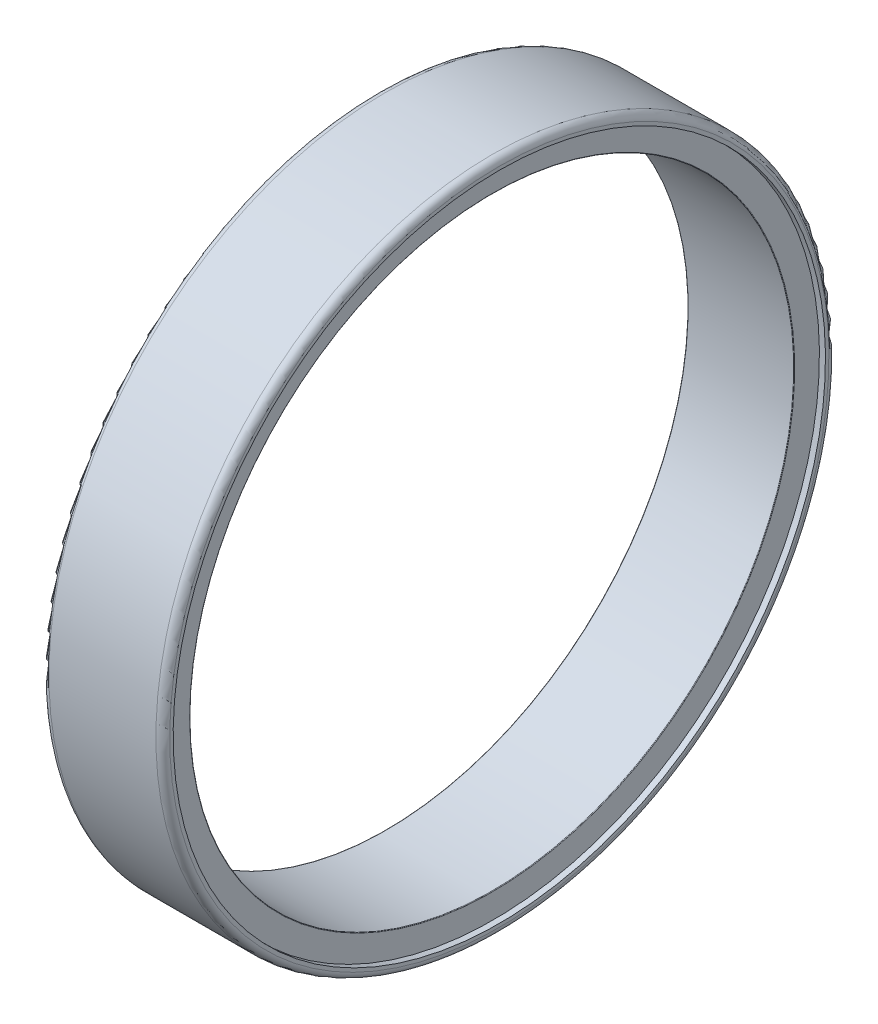
SolidWorks part; units mm, degrees
ref_plane "Plane1" through (0, 0, 0) normal (0, 0, 1) x (1, 0, 0)
ref_plane "Plane2" through (0, 0, 0) normal (0, 1, 0) x (1, 0, 0)
ref_plane "Plane3" through (0, 0, 0) normal (1, 0, 0) x (0, 0, -1)
other "Configuration Table"
sketch "Clipboard" plane through (0, 0, 0) normal (0, 0, 1) x (1, 0, 0)
  line L0 (-10, 0) -> (10, 0) construction
  line L1 (0, 0) -> (22.3471, -0.7804)
  line L2 (0, 0) -> (36.5777, 1.2773)
  line L3 (0, 0) -> (22.3471, -0.7804)
  line L4 (0, 0) -> (-70, -1.2219)
sketch "InnRacSke" plane through (0, 0, 0) normal (0, 0, 1) x (1, 0, 0)
  line L0 (-6.3, 37.8) -> (-7, 37.8)
  line L1 (-7, 37.8) -> (-7, 38.2)
  line L2 (-6.2, 39) -> (6.2, 39)
  line L4 (7, 38.2) -> (7, 37.8)
  line L5 (7, 37.8) -> (6.3, 37.8)
  line L6 (6.3, 37.8) -> (6.3, 38.2)
  line L7 (6.3, 38.2) -> (-6.3, 38.2)
  line L8 (-6.3, 38.2) -> (-6.3, 37.8)
  line L9 (-31.75, 0) -> (31.75, 0) construction
  arc A0 (-7, 38.2) -> (-6.2, 39) centre (-6.2, 38.2) cw
  arc A2 (6.2, 39) -> (7, 38.2) centre (6.2, 38.2) cw
revolve "Race" add sketch "InnRacSke" angle 360 about L9 reverse direction yes
sketch "RolDetSke" plane through (0, 0, 0) normal (0, 0, 1) x (1, 0, 0)
  line L0 (-6.174, 38.1365) -> (-6.174, 36.6)
  line L1 (-6.174, 36.6) -> (6.174, 36.6)
  line L2 (6.174, 36.6) -> (6.174, 38.1365)
  line L3 (6.11, 38.2005) -> (-6.11, 38.2005)
  line L4 (-28.575, 36.6) -> (28.575, 36.6) construction
  arc A0 (6.174, 38.1365) -> (6.11, 38.2005) centre (6.11, 38.1365) ccw
  arc A1 (-6.11, 38.2005) -> (-6.174, 38.1365) centre (-6.11, 38.1365) ccw
  dimension "Roller_length" = 12.348
  dimension "Roller_diameter" = 3.201
revolve "RollerDetailed" [suppressed] add sketch "RolDetSke" angle 360 about L4 reverse direction yes
ref_axis "Axis1" through (-50, 0, 0) along (1, 0, 0)
sketch "CagSpiSke" plane through (0, 0, 0) normal (0, 0, 1) x (1, 0, 0)
  line L0 (6.65, 36.2799) -> (6.65, 36.9201)
  line L1 (6.65, 36.9201) -> (-6.65, 36.9201)
  line L2 (-6.65, 36.9201) -> (-6.65, 36.2799)
  line L3 (-6.65, 36.2799) -> (6.65, 36.2799)
  line L4 (-31.75, 0) -> (31.75, 0) construction
  dimension "halfWidth" = 6.65
revolve "CageSpine" [suppressed] add sketch "CagSpiSke" angle 0.001 about L4
pattern_circular "RollersDetailed" [suppressed] count 2 every 180 about axis through (-50, 0, 0) along (1, 0, 0)
sketch "RolSimSke" plane through (0, 0, 0) normal (0, 0, 1) x (1, 0, 0)
  line L0 (-25.4, 0) -> (25.4, 0) construction
  line L2 (-6.11, 38.201) -> (6.11, 38.201)
  line L3 (-6.174, 38.137) -> (-6.174, 35.064)
  line L4 (-6.11, 35) -> (6.11, 35)
  line L5 (6.174, 38.137) -> (6.174, 35.064)
  arc A0 (-6.174, 35.064) -> (-6.11, 35) centre (-6.11, 35.064) ccw
  arc A1 (-6.11, 38.201) -> (-6.174, 38.137) centre (-6.11, 38.137) ccw
  arc A2 (6.174, 38.137) -> (6.11, 38.201) centre (6.11, 38.137) ccw
  arc A3 (6.11, 35) -> (6.174, 35.064) centre (6.11, 35.064) ccw
  point P10 (-6.174, 35)
  point P15 (6.174, 38.201)
  point P18 (6.174, 35)
  dimension "D1" = 0.064
  dimension "Roller_length" = 12.348
  dimension "Roller_diameter" = 3.201
  dimension "halfWidth" = 6.174
revolve "RollersSimplified" add sketch "RolSimSke" angle 360 about L0
equation "\"BallCLRad@Clipboard\" =  ( \"D1@InnRacSke\" + \"Bore@Clipboard\" )  / 4"
equation "\"RollerCLRad@RolDetSke\" = \"BallCLRad@Clipboard\""
equation "\"halfCyl@InnRacSke\" = \"Cyl_Len@InnRacSke\" / 2"
equation "\"Roller_length@RolDetSke\" = \"Cyl_Len@InnRacSke\" * .98"
equation "\"halfLength@RolDetSke\" = \"Roller_length@RolDetSke\" / 2"
equation "\"Roller_diameter@RolDetSke\" =  ( \"D1@InnRacSke\" - \"Bore@Clipboard\" )  / 2 + .001"
equation "\"Roller_radius@RolDetSke\" = \"Roller_diameter@RolDetSke\" / 50"
equation "\"Cage_width@CagSpiSke\" =  ( \"Cyl_Len@InnRacSke\" + \"Width@InnRacSke\" )  / 2"
equation "\"halfWidth@CagSpiSke\" = \"Cage_width@CagSpiSke\" / 2"
equation "\"Cage_thickness@CagSpiSke\"  = \"Roller_diameter@RolDetSke\" / 5"
equation "\"D2@CagSpiSke\" =  \"RollerCLRad@RolDetSke\" * 2 - \"Cage_thickness@CagSpiSke\""
equation "\"Roller_length@RolSimSke\" = \"Cyl_Len@InnRacSke\" * .98"
equation "\"halfWidth@RolSimSke\" = \"Roller_length@RolSimSke\" / 2"
equation "\"D1@RolSimSke\" = \"Roller_radius@RolDetSke\""
equation "\"Roller_diameter@RolSimSke\" =  ( \"D1@InnRacSke\" - \"Bore@Clipboard\" )  / 2 + .001"
equation "\"Bore@RolSimSke\" = \"Bore@Clipboard\""
equation "\"Max_count@Clipboard\" = int( 3.14159265 / atn(( \"Roller_diameter@RolDetSke\" / 2) / sqr( \"RollerCLRad@RolDetSke\"  *  \"RollerCLRad@RolDetSke\" - ( \"Roller_diameter@RolDetSke\" / 2) *  ( \"Roller_diameter@RolDetSke\" / 2))))"
equation "\"Max_count@Clipboard\" = ((sgn( \"Max_count@Clipboard\" - \"Count@Clipboard\" )-1)*( \"Max_count@Clipboard\" - \"Count@Clipboard\" ))/-2+ \"Count@Clipboard\""
equation "\"Count@RollersDetailed\" = int( \"Show_count@Clipboard\" ) "
equation "\"Count@RollersDetailed\" = ((sgn( \"Count@RollersDetailed\" - \"Max_count@Clipboard\" )-1)*( \"Count@RollersDetailed\" - \"Max_count@Clipboard\" ))/-2+ \"Max_count@Clipboard\""
equation "\"Count@RollersDetailed\" = ((sgn( \"Count@RollersDetailed\" - \"Min_count@Clipboard\" )+1)*( \"Count@RollersDetailed\" - \"Min_count@Clipboard\"))/2 +\"Min_count@Clipboard\""
equation "\"Angle@RollersDetailed\" = 360.0 / \"Max_count@Clipboard\""
equation "\"Angle@CageSpine\" =  \"Angle@RollersDetailed\" * ( \"Count@RollersDetailed\" -1 + int( \"Count@RollersDetailed\" / \"Max_count@Clipboard\" ) )  + 0.001 -  int( \"Count@RollersDetailed\" / \"Max_count@Clipboard\" ) * 0.001"
equation "\"Angle@CageSpine\" =  \"Angle@CageSpine\" * int( \"Min_count@Clipboard\" / 2) + int(1 / \"Min_count@Clipboard\")  * 0.001"
